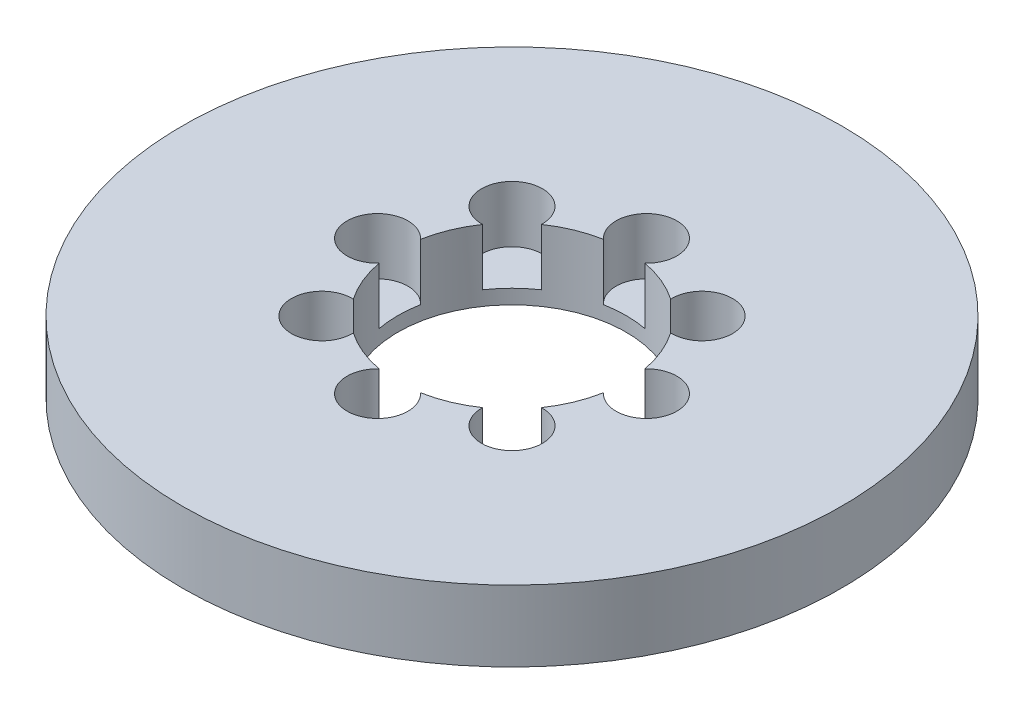
SolidWorks part; units mm, degrees
ref_plane "Front Plane" through (0, 0, 0) normal (0, 0, 1) x (1, 0, 0)
ref_plane "Top Plane" through (0, 0, 0) normal (0, 1, 0) x (1, 0, 0)
ref_plane "Right Plane" through (0, 0, 0) normal (1, 0, 0) x (0, 0, -1)
sketch "Sketch1" plane through (0, 0, 0) normal (0, 1, 0) x (1, 0, 0)
  circle A0 centre (0, 0) radius 65
  dimension "FLANGE_OD" = 130
extrude "Boss-Extrude1" add sketch "Sketch1" along normal blind 14
sketch "Sketch2" plane through (0, 0, 0) normal (0, 1, 0) x (1, 0, 0)
  circle A0 centre (0, 0) radius 22.5
  dimension "BORE_D" = 45
extrude "Cut-Extrude1" cut sketch "Sketch2" along normal through all
sketch "Sketch3" plane through (0, 14, 0) normal (0, 1, 0) x (1, 0, 0)
  circle A0 centre (0, 0) radius 26.5192 construction
  circle A1 centre (-26.5192, 0) radius 6.0031
  dimension "BOLT_D" = 12.0062
  dimension "BOLT_PCD" = 53.0383
extrude "Cut-Extrude2" cut sketch "Sketch3" against normal blind 11.1602
pattern_circular "CirPattern1" count 8 over 360 about axis through (0, 0, 0) along (0, 1, 0) of "Cut-Extrude2"
